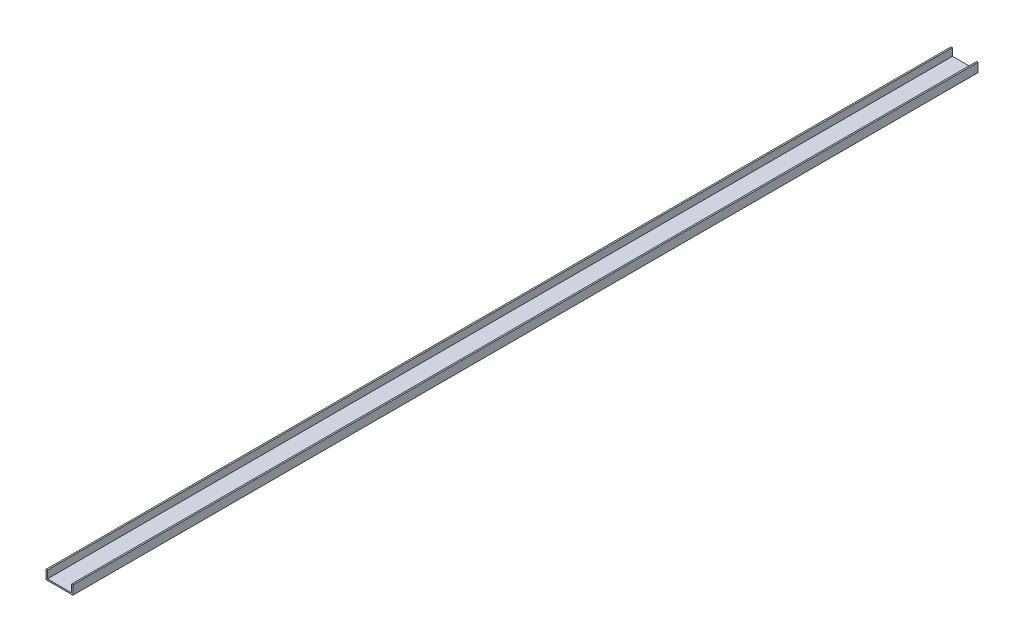
SolidWorks part; units mm, degrees
ref_plane "Front" through (0, 0, 0) normal (0, 0, 1) x (1, 0, 0)
ref_plane "Top" through (0, 0, 0) normal (0, 1, 0) x (1, 0, 0)
ref_plane "Right" through (0, 0, 0) normal (1, 0, 0) x (0, 0, -1)
sketch "Sketch1" plane through (0, 0, 0) normal (0, 0, 1) x (1, 0, 0)
  line L0 (-68.2625, 0) -> (68.2625, 0)
  line L1 (-76.2, -7.9375) -> (76.2, -7.9375)
  line L2 (0, -7.9375) -> (0, 0) construction
  line L3 (-76.2, -7.9375) -> (-76.2, 42.8625)
  line L4 (-76.2, 42.8625) -> (-68.2625, 42.8625)
  line L5 (-68.2625, 42.8625) -> (-68.2625, 0)
  line L6 (76.2, -7.9375) -> (76.2, 42.8625)
  line L7 (76.2, 42.8625) -> (68.2625, 42.8625)
  line L8 (68.2625, 42.8625) -> (68.2625, 0)
  dimension "Width" = 152.4
  dimension "Height" = 50.8
  dimension "Wall Thickness" = 7.9375
sketch "Sketch2" plane through (0, 0, 0) normal (1, 0, 0) x (0, 0, -1)
  line L0 (914.4, 0) -> (-914.4, 0) construction
  dimension "Length" = 1828.8
sketch "Sketch3" plane through (0, 0, 0) normal (0, 0, 1) x (1, 0, 0)
  line L0 (-68.2625, 42.8625) -> (-68.2625, 0) construction
  line L1 (-68.2625, 0) -> (68.2625, 0) construction
  line L2 (68.2625, 42.8625) -> (68.2625, 0) construction
  line L3 (76.2, 42.8625) -> (68.2625, 42.8625) construction
  line L4 (76.2, -7.9375) -> (76.2, 42.8625) construction
  line L5 (-76.2, -7.9375) -> (76.2, -7.9375) construction
  line L6 (-76.2, -7.9375) -> (-76.2, 42.8625) construction
  line L7 (-76.2, 42.8625) -> (-68.2625, 42.8625) construction
  line L8 (-68.2625, 42.8625) -> (-68.2625, 0)
  line L9 (-68.2625, 0) -> (68.2625, 0)
  line L10 (68.2625, 42.8625) -> (68.2625, 0)
  line L11 (76.2, 42.8625) -> (68.2625, 42.8625)
  line L12 (76.2, -7.9375) -> (76.2, 42.8625)
  line L13 (-76.2, -7.9375) -> (76.2, -7.9375)
  line L14 (-76.2, -7.9375) -> (-76.2, 42.8625)
  line L15 (-76.2, 42.8625) -> (-68.2625, 42.8625)
extrude "Boss-Extrude1" add sketch "Sketch3" along normal blind 5124.45
sketch "Sketch4" plane through (0, 0, 0) normal (0, 0, 1) x (1, 0, 0)
  line L0 (76.2, 42.8625) -> (76.2, 0) construction
  line L1 (68.2625, 0) -> (-68.2625, 0) construction
  line L2 (76.2, -7.9375) -> (68.2625, -7.9375) construction
  line L3 (-76.2, -7.9375) -> (76.2, -7.9375) construction
  line L4 (68.2625, 42.8625) -> (68.2625, 0) construction
